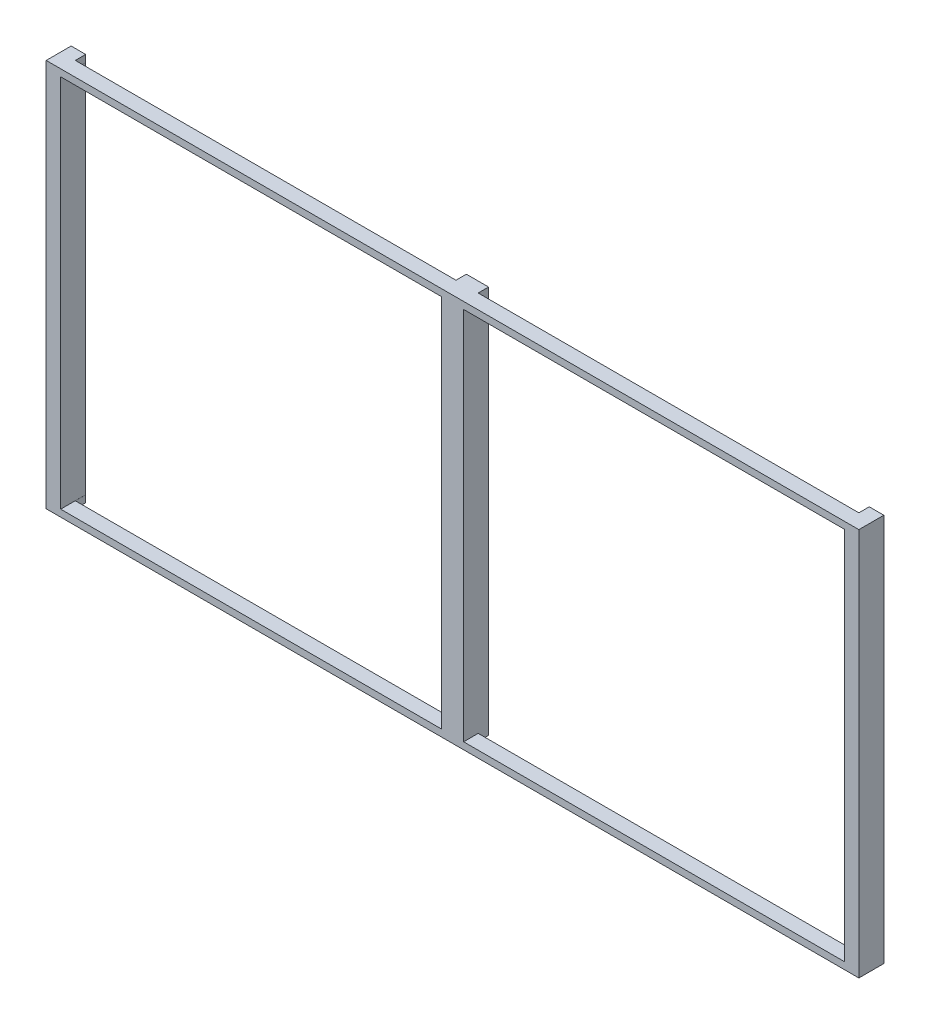
SolidWorks part; units mm, degrees
ref_plane "Спереди" through (0, 0, 0) normal (0, 0, 1) x (1, 0, 0)
ref_plane "Сверху" through (0, 0, 0) normal (0, 1, 0) x (1, 0, 0)
ref_plane "Справа" through (0, 0, 0) normal (1, 0, 0) x (0, 0, -1)
sketch "Эскиз1" plane through (0, 0, 0) normal (0, 0, 1) x (1, 0, 0)
  line L1 (-2930, 1400) -> (2930, 1400)
  line L2 (-2930, 1400) -> (-2930, -1400)
  line L3 (-2930, -1400) -> (2930, -1400)
  line L4 (2930, 1400) -> (2930, -1400)
  line L5 (-2930, 1400) -> (2930, -1400) construction
  line L6 (-2930, -1400) -> (2930, 1400) construction
  line L7 (-2825.3571, 1350) -> (-80, 1350)
  line L8 (-2825.3571, 1350) -> (-2825.3571, -1350)
  line L9 (-2825.3571, -1350) -> (-80, -1350)
  line L10 (-80, 1350) -> (-80, -1350)
  line L11 (80, 1350) -> (2825.3571, 1350)
  line L12 (80, 1350) -> (80, -1350)
  line L13 (80, -1350) -> (2825.3571, -1350)
  line L14 (2825.3571, 1350) -> (2825.3571, -1350)
  point P0 (0, 0)
extrude "Бобышка-Вытянуть1" add sketch "Эскиз1" along normal blind 180
sketch "Эскиз2" plane through (0, -1400, 0) normal (0, -1, 0) x (1, 0, 0)
  line L2 (-2825, 75) -> (-80, 75)
  line L3 (-2825, 75) -> (-2825, 0)
  line L4 (-2825, 0) -> (-80, 0)
  line L5 (-80, 75) -> (-80, 0)
  line L6 (-2825, 75) -> (-80, 0) construction
  line L7 (-2825, 0) -> (-80, 75) construction
  line L8 (0, 424.0898) -> (0, -233.7336) construction
  line L9 (2825, 0) -> (80, 75) construction
  line L10 (2825, 75) -> (80, 0) construction
  line L11 (80, 75) -> (80, 0)
  line L12 (2825, 0) -> (80, 0)
  line L13 (2825, 75) -> (2825, 0)
  line L14 (2825, 75) -> (80, 75)
  line L15 (-2930, 0) -> (2930, 0) construction
  point P1 (-2824.1869, 72.4908)
  point P2 (-1452.5, 37.5)
  point P8 (0, 0)
  point P15 (1452.5, 37.5)
  point P16 (0, 0)
  point P17 (-2825.3571, 0)
  point P20 (0, 0)
extrude "Вырез-Вытянуть1" cut sketch "Эскиз2" against normal through all
